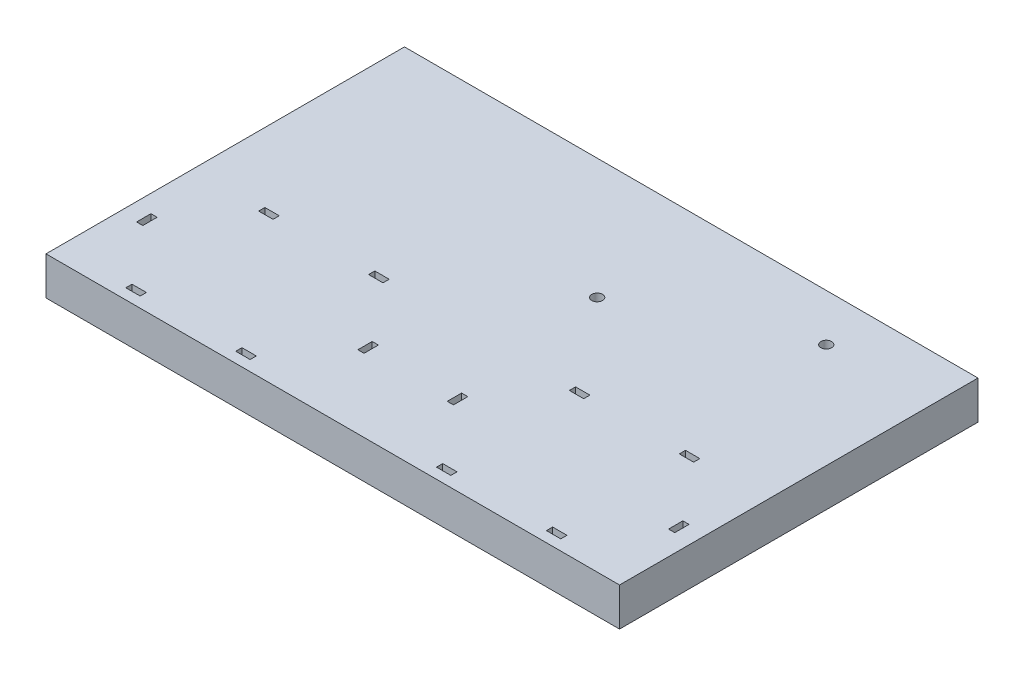
SolidWorks part; units mm, degrees
ref_plane "Front Plane" through (0, 0, 0) normal (0, 0, 1) x (1, 0, 0)
ref_plane "Top Plane" through (0, 0, 0) normal (0, 1, 0) x (1, 0, 0)
ref_plane "Right Plane" through (0, 0, 0) normal (1, 0, 0) x (0, 0, -1)
sketch "Sketch1" plane through (0, 0, 0) normal (0, 1, 0) x (1, 0, 0)
  line L0 (-66.0627, 0) -> (65.2437, 0) construction
  line L1 (-60, 37.5) -> (60, 37.5)
  line L2 (-60, 37.5) -> (-60, -37.5)
  line L3 (-60, -37.5) -> (60, -37.5)
  line L4 (60, 37.5) -> (60, -37.5)
  line L5 (32.5, -7.5) -> (32.5, -34) construction
  line L6 (10, -7.5) -> (55, -7.5) construction
  line L7 (10, -7.5) -> (10, -34) construction
  line L8 (10, -34) -> (55, -34) construction
  line L9 (55, -7.5) -> (55, -34) construction
  line L10 (-5.21, 30.09) -> (40, 30.09) construction
  line L11 (-5.21, 30.09) -> (-5.21, 10) construction
  line L12 (-5.21, 10) -> (40, 10) construction
  line L13 (40, 30.09) -> (40, 10) construction
  line L14 (-5.21, 30.09) -> (40, 10) construction
  line L15 (-5.21, 10) -> (40, 30.09) construction
  line L16 (10, -20.75) -> (55, -20.75) construction
  line L17 (19.5, -35.3) -> (22.5, -35.3)
  line L18 (19.5, -7.5) -> (22.5, -7.5)
  line L19 (19.5, -7.5) -> (19.5, -6.2)
  line L20 (19.5, -6.2) -> (22.5, -6.2)
  line L21 (22.5, -7.5) -> (22.5, -6.2)
  line L22 (22.5, -34) -> (22.5, -35.3)
  line L23 (19.5, -34) -> (22.5, -34)
  line L24 (19.5, -34) -> (19.5, -35.3)
  line L25 (45.5, -7.5) -> (45.5, -6.2)
  line L26 (45.5, -6.2) -> (42.5, -6.2)
  line L27 (45.5, -7.5) -> (42.5, -7.5)
  line L28 (42.5, -7.5) -> (42.5, -6.2)
  line L29 (45.5, -34) -> (45.5, -35.3)
  line L30 (42.5, -34) -> (42.5, -35.3)
  line L31 (45.5, -34) -> (42.5, -34)
  line L32 (45.5, -35.3) -> (42.5, -35.3)
  line L33 (56.3, -22.25) -> (55, -22.25)
  line L34 (8.7, -19.25) -> (10, -19.25)
  line L35 (8.7, -19.25) -> (8.7, -22.25)
  line L36 (8.7, -22.25) -> (10, -22.25)
  line L37 (10, -19.25) -> (10, -22.25)
  line L38 (56.3, -19.25) -> (55, -19.25)
  line L39 (56.3, -19.25) -> (56.3, -22.25)
  line L40 (55, -19.25) -> (55, -22.25)
  line L41 (0, -62.4684) -> (0, 56.3378) construction
  line L48 (-55, -19.25) -> (-55, -22.25)
  line L49 (-56.3, -19.25) -> (-56.3, -22.25)
  line L50 (-56.3, -19.25) -> (-55, -19.25)
  line L51 (-10, -19.25) -> (-10, -22.25)
  line L52 (-8.7, -22.25) -> (-10, -22.25)
  line L53 (-8.7, -19.25) -> (-8.7, -22.25)
  line L54 (-8.7, -19.25) -> (-10, -19.25)
  line L55 (-56.3, -22.25) -> (-55, -22.25)
  line L56 (-45.5, -35.3) -> (-42.5, -35.3)
  line L57 (-45.5, -34) -> (-42.5, -34)
  line L58 (-42.5, -34) -> (-42.5, -35.3)
  line L59 (-45.5, -34) -> (-45.5, -35.3)
  line L60 (-42.5, -7.5) -> (-42.5, -6.2)
  line L61 (-45.5, -7.5) -> (-42.5, -7.5)
  line L62 (-45.5, -6.2) -> (-42.5, -6.2)
  line L63 (-45.5, -7.5) -> (-45.5, -6.2)
  line L64 (-19.5, -34) -> (-19.5, -35.3)
  line L65 (-19.5, -34) -> (-22.5, -34)
  line L66 (-22.5, -34) -> (-22.5, -35.3)
  line L67 (-22.5, -7.5) -> (-22.5, -6.2)
  line L68 (-19.5, -6.2) -> (-22.5, -6.2)
  line L69 (-19.5, -7.5) -> (-19.5, -6.2)
  line L70 (-19.5, -7.5) -> (-22.5, -7.5)
  line L71 (-19.5, -35.3) -> (-22.5, -35.3)
  circle A2 centre (38.07, 27.68) radius 1.13
  circle A3 centre (5.56, 12.26) radius 1.13
  point P4 (60, 0)
  point P6 (0, 37.5)
  point P23 (17.395, 20.045)
  point P46 (10, -20.75)
  point P53 (0, -37.5)
  dimension "D5" = 5
  dimension "D17" = 2.26
  dimension "D18" = 2.26
  dimension "D1" = 120
  dimension "D2" = 75
  dimension "D3" = 26.5
  dimension "D4" = 45
  dimension "D6" = 7.5
  dimension "D7" = 20
  dimension "D8" = 1.3
  dimension "D9" = 3
  dimension "D13" = 45.21
  dimension "D14" = 20.09
  dimension "D15" = 10
  dimension "D16" = 20
  dimension "D19" = 15.42
  dimension "D20" = 17.68
  dimension "D21" = 32.51
  dimension "D22" = 1.93
extrude "Boss-Extrude1" add sketch "Sketch1" along normal blind 8
